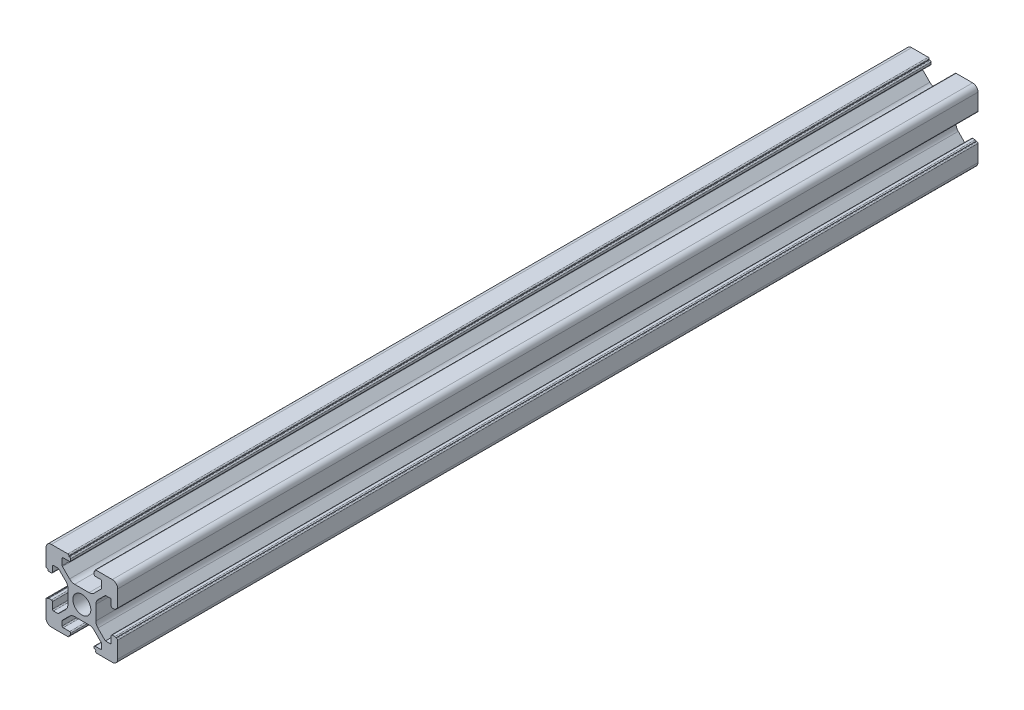
SolidWorks part; units mm, degrees
ref_plane "Front Plane" through (0, 0, 0) normal (0, 0, 1) x (1, 0, 0)
ref_plane "Top Plane" through (0, 0, 0) normal (0, 1, 0) x (1, 0, 0)
ref_plane "Right Plane" through (0, 0, 0) normal (1, 0, 0) x (0, 0, -1)
sketch "Model" plane through (0, 0, 0) normal (0, 0, 1) x (1, 0, 0)
  line L0 (3.9, -0.3) -> (3.9, -2.3109)
  line L1 (4.4858, -3.7251) -> (6.5607, -5.8)
  line L2 (6.5607, -5.8) -> (7.9, -5.8)
  line L3 (8.2, -5.5) -> (8.2, -3.7)
  line L4 (8.5, -3.4) -> (9.2, -3.4)
  line L5 (9.5, -3.7) -> (9.5, -3.6)
  line L6 (9.5, -3.6) -> (9.7, -3.6)
  line L7 (10, -3.9) -> (10, -8.5)
  line L8 (8.5, -10) -> (4.1583, -10)
  line L9 (3.4, -9) -> (3.4, -8.8)
  line L10 (3.7, -8.5) -> (5.2, -8.5)
  line L11 (5.5, -8.2) -> (5.5, -6.9849)
  line L12 (5.4121, -6.7728) -> (3.4251, -4.7858)
  line L13 (2.0109, -4.2) -> (0, -4.2)
  line L14 (0, -4.2) -> (-2.0109, -4.2)
  line L15 (-3.4251, -4.7858) -> (-5.4121, -6.7728)
  line L16 (-5.5, -6.9849) -> (-5.5, -8.2)
  line L17 (-5.2, -8.5) -> (-3.4, -8.5)
  line L18 (-3.1, -8.8) -> (-3.1, -9.2)
  line L19 (-3.9, -10) -> (-8.5, -10)
  line L20 (-10, -8.5) -> (-10, -3.9)
  line L21 (-9.7, -3.6) -> (-9.5, -3.6)
  line L22 (-9.5, -3.6) -> (-9.5, -3.7)
  line L23 (-9.2, -3.4) -> (-8.5, -3.4)
  line L24 (-8.2, -3.7) -> (-8.2, -5.5)
  line L25 (-7.9, -5.8) -> (-6.6849, -5.8)
  line L26 (-6.4728, -5.7121) -> (-4.4858, -3.7251)
  line L27 (-3.9, -2.3109) -> (-3.9, -0.3)
  line L28 (-3.9, -0.3) -> (-3.9, 1.7109)
  line L29 (-4.4858, 3.1251) -> (-6.4728, 5.1121)
  line L30 (-6.6849, 5.2) -> (-7.9, 5.2)
  line L31 (-8.2, 4.9) -> (-8.2, 3.4)
  line L32 (-8.5, 3.1) -> (-9.2, 3.1)
  line L33 (-9.5, 3.4) -> (-9.5, 3.6)
  line L34 (-9.5, 3.6) -> (-9.7, 3.6)
  line L35 (-10, 3.9) -> (-10, 8.5)
  line L36 (-8.5, 10) -> (-3.9, 10)
  line L37 (-3.6, 9.7) -> (-3.6, 9.5)
  line L38 (-3.6, 9.5) -> (-3.4, 9.5)
  line L39 (-3.1, 9.2) -> (-3.1, 8.7)
  line L40 (-3.4, 8.4) -> (-5.2, 8.4)
  line L41 (-5.5, 8.1) -> (-5.5, 6.3849)
  line L42 (-5.4121, 6.1728) -> (-3.4251, 4.1858)
  line L43 (-2.0109, 3.6) -> (0, 3.6)
  line L44 (0, 3.6) -> (2.0109, 3.6)
  line L45 (3.4251, 4.1858) -> (5.4121, 6.1728)
  line L46 (5.5, 6.3849) -> (5.5, 8.1)
  line L47 (5.2, 8.4) -> (3.7, 8.4)
  line L48 (3.4, 8.7) -> (3.4, 9.2)
  line L49 (3.7, 9.5) -> (3.6, 9.5)
  line L50 (3.6, 9.5) -> (3.6, 9.7)
  line L51 (3.9, 10) -> (8.5, 10)
  line L52 (10, 8.5) -> (10, 3.9)
  line L53 (9.7, 3.6) -> (9.5, 3.6)
  line L54 (9.5, 3.6) -> (9.5, 3.4)
  line L55 (9.2, 3.1) -> (8.5, 3.1)
  line L56 (8.2, 3.4) -> (8.2, 4.9)
  line L57 (7.9, 5.2) -> (6.6849, 5.2)
  line L58 (6.4728, 5.1121) -> (4.4858, 3.1251)
  line L59 (3.9, 1.7109) -> (3.9, -0.3)
  line L60 (-3.9, -0.3) -> (3.9, -0.3) construction
  line L61 (0, 3.6) -> (0, -4.2) construction
  circle A0 centre (0, -0.3) radius 2.5
  arc A1 (3.9, -2.3109) -> (4.4858, -3.7251) centre (5.9, -2.3109) ccw
  arc A2 (7.9, -5.8) -> (8.2, -5.5) centre (7.9, -5.5) ccw
  arc A3 (8.5, -3.4) -> (8.2, -3.7) centre (8.5, -3.7) ccw
  arc A4 (9.5, -3.7) -> (9.2, -3.4) centre (9.2, -3.7) ccw
  arc A5 (10, -3.9) -> (9.7, -3.6) centre (9.7, -3.9) ccw
  arc A6 (8.5, -10) -> (10, -8.5) centre (8.5, -8.5) ccw
  arc A7 (3.8833, -9.58) -> (4.1583, -10) centre (4.1583, -9.7) ccw
  arc A8 (3.8833, -9.58) -> (3.7, -9.3) centre (3.7, -9.5) ccw
  arc A9 (3.4, -9) -> (3.7, -9.3) centre (3.7, -9) ccw
  arc A10 (3.7, -8.5) -> (3.4, -8.8) centre (3.7, -8.8) ccw
  arc A11 (5.2, -8.5) -> (5.5, -8.2) centre (5.2, -8.2) ccw
  arc A12 (5.5, -6.9849) -> (5.4121, -6.7728) centre (5.2, -6.9849) ccw
  arc A13 (3.4251, -4.7858) -> (2.0109, -4.2) centre (2.0109, -6.2) ccw
  arc A14 (-2.0109, -4.2) -> (-3.4251, -4.7858) centre (-2.0109, -6.2) ccw
  arc A15 (-5.4121, -6.7728) -> (-5.5, -6.9849) centre (-5.2, -6.9849) ccw
  arc A16 (-5.5, -8.2) -> (-5.2, -8.5) centre (-5.2, -8.2) ccw
  arc A17 (-3.1, -8.8) -> (-3.4, -8.5) centre (-3.4, -8.8) ccw
  arc A18 (-3.4, -9.5) -> (-3.1, -9.2) centre (-3.4, -9.2) ccw
  arc A19 (-3.4, -9.5) -> (-3.6, -9.7) centre (-3.4, -9.7) ccw
  arc A20 (-3.9, -10) -> (-3.6, -9.7) centre (-3.9, -9.7) ccw
  arc A21 (-10, -8.5) -> (-8.5, -10) centre (-8.5, -8.5) ccw
  arc A22 (-9.7, -3.6) -> (-10, -3.9) centre (-9.7, -3.9) ccw
  arc A23 (-9.2, -3.4) -> (-9.5, -3.7) centre (-9.2, -3.7) ccw
  arc A24 (-8.2, -3.7) -> (-8.5, -3.4) centre (-8.5, -3.7) ccw
  arc A25 (-8.2, -5.5) -> (-7.9, -5.8) centre (-7.9, -5.5) ccw
  arc A26 (-6.6849, -5.8) -> (-6.4728, -5.7121) centre (-6.6849, -5.5) ccw
  arc A27 (-4.4858, -3.7251) -> (-3.9, -2.3109) centre (-5.9, -2.3109) ccw
  arc A28 (-3.9, 1.7109) -> (-4.4858, 3.1251) centre (-5.9, 1.7109) ccw
  arc A29 (-6.4728, 5.1121) -> (-6.6849, 5.2) centre (-6.6849, 4.9) ccw
  arc A30 (-7.9, 5.2) -> (-8.2, 4.9) centre (-7.9, 4.9) ccw
  arc A31 (-8.5, 3.1) -> (-8.2, 3.4) centre (-8.5, 3.4) ccw
  arc A32 (-9.5, 3.4) -> (-9.2, 3.1) centre (-9.2, 3.4) ccw
  arc A33 (-10, 3.9) -> (-9.7, 3.6) centre (-9.7, 3.9) ccw
  arc A34 (-8.5, 10) -> (-10, 8.5) centre (-8.5, 8.5) ccw
  arc A35 (-3.6, 9.7) -> (-3.9, 10) centre (-3.9, 9.7) ccw
  arc A36 (-3.1, 9.2) -> (-3.4, 9.5) centre (-3.4, 9.2) ccw
  arc A37 (-3.4, 8.4) -> (-3.1, 8.7) centre (-3.4, 8.7) ccw
  arc A38 (-5.2, 8.4) -> (-5.5, 8.1) centre (-5.2, 8.1) ccw
  arc A39 (-5.5, 6.3849) -> (-5.4121, 6.1728) centre (-5.2, 6.3849) ccw
  arc A40 (-3.4251, 4.1858) -> (-2.0109, 3.6) centre (-2.0109, 5.6) ccw
  arc A41 (2.0109, 3.6) -> (3.4251, 4.1858) centre (2.0109, 5.6) ccw
  arc A42 (5.4121, 6.1728) -> (5.5, 6.3849) centre (5.2, 6.3849) ccw
  arc A43 (5.5, 8.1) -> (5.2, 8.4) centre (5.2, 8.1) ccw
  arc A44 (3.4, 8.7) -> (3.7, 8.4) centre (3.7, 8.7) ccw
  arc A45 (3.7, 9.5) -> (3.4, 9.2) centre (3.7, 9.2) ccw
  arc A46 (3.9, 10) -> (3.6, 9.7) centre (3.9, 9.7) ccw
  arc A47 (10, 8.5) -> (8.5, 10) centre (8.5, 8.5) ccw
  arc A48 (9.7, 3.6) -> (10, 3.9) centre (9.7, 3.9) ccw
  arc A49 (9.2, 3.1) -> (9.5, 3.4) centre (9.2, 3.4) ccw
  arc A50 (8.2, 3.4) -> (8.5, 3.1) centre (8.5, 3.4) ccw
  arc A51 (8.2, 4.9) -> (7.9, 5.2) centre (7.9, 4.9) ccw
  arc A52 (6.6849, 5.2) -> (6.4728, 5.1121) centre (6.6849, 4.9) ccw
  arc A53 (4.4858, 3.1251) -> (3.9, 1.7109) centre (5.9, 1.7109) ccw
  dimension "D1" = 5
  dimension "D2" = 20
  dimension "D3" = 20
  dimension "D4" = 6.5
  dimension "D5" = 6.5
  dimension "D6" = 11
  dimension "D7" = 11
extrude "Boss-Extrude1" add sketch "Model" along normal blind 240
equation "\"Width\"= 20mm"
equation "\"Length\"= 240mm"
equation "\"D1@Boss-Extrude1\"=\"Length\""
equation "\"Internal_hole_diameter\"= 5mm"
equation "\"Slot width\"= 6.5mm"
equation "\"D1@Model\"=\"Internal_hole_diameter\""
equation "\"D2@Model\"=\"Width\""
equation "\"D3@Model\"=\"Width\""
equation "\"D4@Model\"=\"Slot width\""
equation "\"D5@Model\"=\"Slot width\""
equation "\"Internal_Slot_width\"= 11mm"
equation "\"D6@Model\"=\"Internal_Slot_width\""
equation "\"D7@Model\"=\"Internal_Slot_width\""
